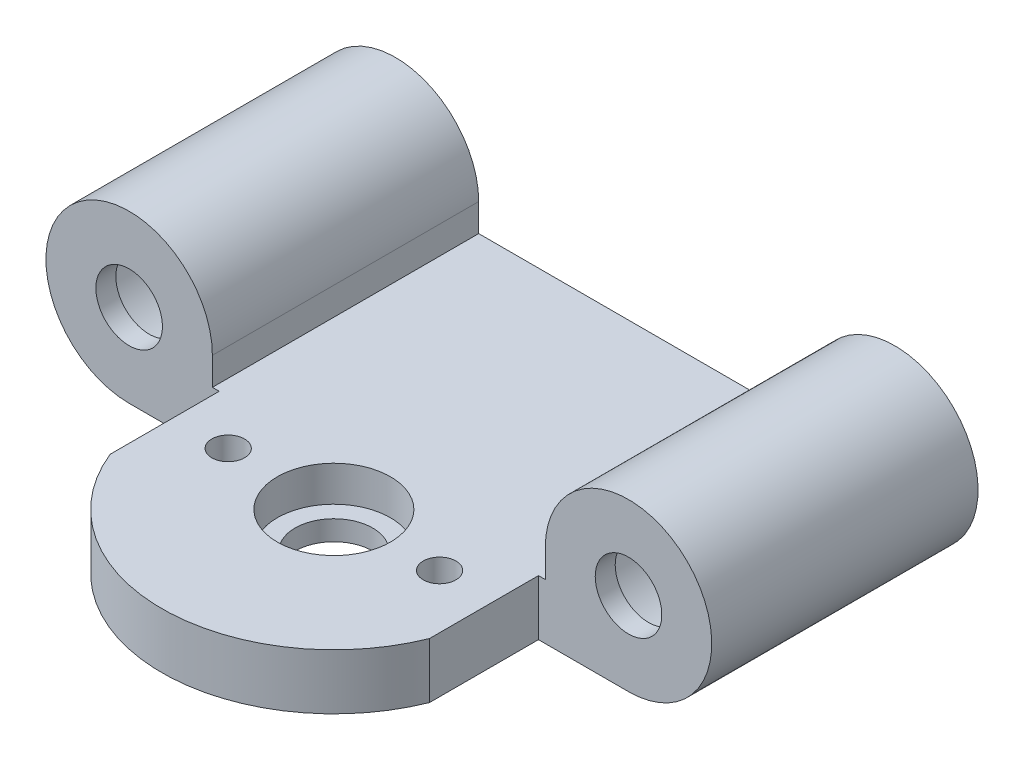
SolidWorks part; units mm, degrees
ref_plane "Plan de face" through (0, 0, 0) normal (0, 0, 1) x (1, 0, 0)
ref_plane "Plan de dessus" through (0, 0, 0) normal (0, 1, 0) x (1, 0, 0)
ref_plane "Plan de droite" through (0, 0, 0) normal (1, 0, 0) x (0, 0, -1)
sketch "Esquisse1" plane through (0, 0, 0) normal (0, 1, 0) x (1, 0, 0)
  line L1 (-14.385, -5.7725) -> (-14.385, 28.05)
  line L2 (14.385, -5.7725) -> (14.385, 28.05)
  line L3 (-14.385, 28.05) -> (14.385, 28.05)
  line L4 (-14.385, -5.7725) -> (14.385, -5.7725) construction
  line L5 (0, 0) -> (-14.385, 0) construction
  line L6 (0, 0) -> (0, -15.5) construction
  circle A0 centre (0, 0) radius 15.5 construction
  arc A1 (-14.385, -5.7725) -> (14.385, -5.7725) centre (0, 0) ccw
  circle A2 centre (0, 0) radius 3.5
  point P10 (0, 0)
  point P12 (1.6052, -15.4167)
  point P14 (0, -0.0963)
  dimension "D1" = 31
  dimension "D3" = 7
  dimension "D2" = 28.77
  dimension "D4" = 28.05
extrude "Boss.-Extru.1" add sketch "Esquisse1" along normal blind 5
sketch "Esquisse2" plane through (0, 5, 0) normal (0, 1, 0) x (1, 0, 0)
  circle A0 centre (0, 0) radius 5.1
  point P2 (0, 0)
  dimension "D1" = 10.2
extrude "Enlèv. mat.-Extru.1" cut sketch "Esquisse2" against normal blind 3.2
sketch "Esquisse3" plane through (0, 5, 0) normal (0, 1, 0) x (1, 0, 0)
  line L0 (9.525, 0) -> (-9.525, 0) construction
  circle A0 centre (-9.525, 0) radius 1.475
  circle A1 centre (9.525, 0) radius 1.475
  point P4 (9.8447, 0)
  point P8 (0, 0)
  dimension "D1" = 2.95
  dimension "D2" = 19.05
extrude "Enlèv. mat.-Extru.2" cut sketch "Esquisse3" against normal blind 4
sketch "Esquisse4" plane through (0, 0, -28.05) normal (0, 0, -1) x (-1, 0, 0)
  line L0 (30, 0) -> (15, 15) construction
  line L1 (15, 0) -> (30, 0) construction
  line L3 (15, 15) -> (30, 15) construction
  line L4 (30, 0) -> (30, 15) construction
  line L5 (-15, 0) -> (-30, 0) construction
  line L6 (-15, 0) -> (-15, 15) construction
  line L7 (-15, 15) -> (-30, 15) construction
  line L8 (-30, 0) -> (-30, 15) construction
  line L9 (-15, 15) -> (-30, 0) construction
  line L10 (-15, 0) -> (15, 0) construction
  line L12 (-14.385, 0) -> (-15, 0) construction
  line L13 (-14.385, 0) -> (-14.385, 5)
  line L14 (-14.385, 5) -> (-15, 5)
  line L15 (-15, 0) -> (-15, 5) construction
  line L17 (14.385, 0) -> (14.385, 5)
  line L18 (14.385, 5) -> (15, 5)
  line L19 (15, 0) -> (15, 5) construction
  line L20 (15, 15) -> (15, 5) construction
  line L21 (15, 5) -> (15, 7.5)
  line L23 (14.385, 0) -> (22.5, 0)
  line L24 (-14.385, 0) -> (-22.5, 0)
  line L25 (-15, 7.5) -> (-15, 5)
  circle A0 centre (22.5, 7.5) radius 3
  circle A1 centre (-22.5, 7.5) radius 3
  circle A2 centre (22.5, 7.5) radius 7.5 construction
  arc A3 (22.5, 0) -> (15, 7.5) centre (22.5, 7.5) ccw
  arc A4 (-15, 7.5) -> (-22.5, 0) centre (-22.5, 7.5) ccw
  point P18 (0, 0)
  point P29 (-23.5, 0)
  point P30 (15, 8.5)
  line M11 (14.385, 0) -> (14.385, 5)
  line M13 (-14.385, 5) -> (-14.385, 0)
  dimension "D3" = 6
  dimension "D1" = 15
  dimension "D4" = 30
extrude "Boss.-Extru.2" add sketch "Esquisse4" against normal blind 24 contours L14 L7 L8 L5 L12 A1 M13 | L3 L20 L18 L1 L4 A0 M11 region at (18.4425, 0.2165, -28.05) region at (-14.6015, 2.5, -28.05)
sketch "Esquisse5" plane through (0, 0, -28.05) normal (0, 0, -1) x (-1, 0, 0)
  circle A0 centre (22.5, 7.5) radius 6.1
  circle A1 centre (-22.5, 7.5) radius 6.1
  dimension "D1" = 12.2
extrude "Enlèv. mat.-Extru.3" cut sketch "Esquisse5" against normal blind 22.2
